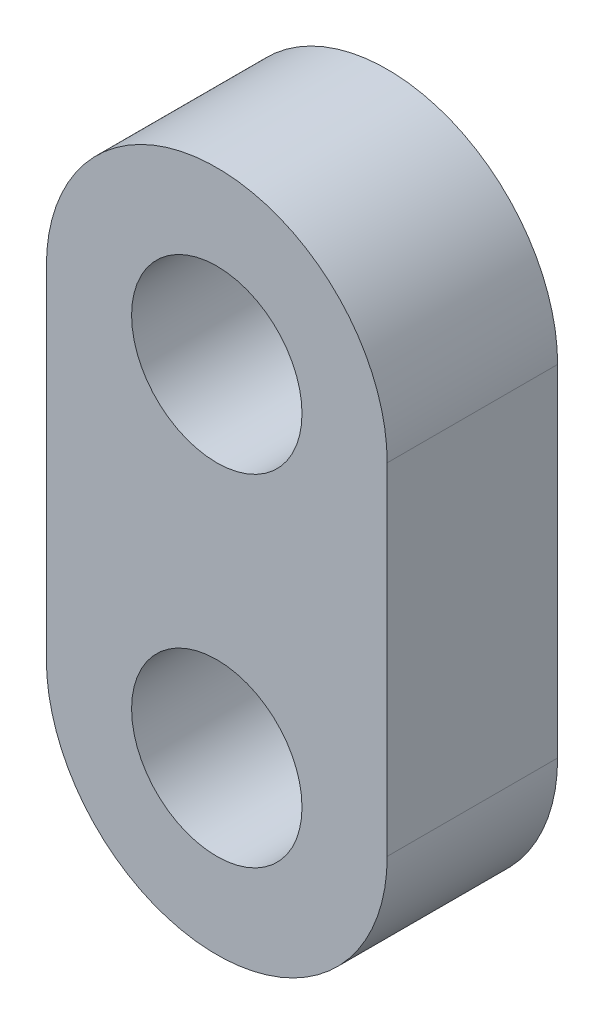
SolidWorks part; units mm, degrees
ref_plane "Front Plane" through (0, 0, 0) normal (0, 0, 1) x (1, 0, 0)
ref_plane "Top Plane" through (0, 0, 0) normal (0, 1, 0) x (1, 0, 0)
ref_plane "Right Plane" through (0, 0, 0) normal (1, 0, 0) x (0, 0, -1)
sketch "Sketch1" plane through (0, 0, 0) normal (0, 0, 1) x (1, 0, 0)
  line L0 (0, 0) -> (0, 12.7) construction
  line L1 (-6.35, 12.7) -> (-6.35, 0)
  line L2 (6.35, 12.7) -> (6.35, 0)
  circle A0 centre (0, 0) radius 3.175
  circle A1 centre (0, 12.7) radius 3.175
  arc A2 (6.35, 12.7) -> (-6.35, 12.7) centre (0, 12.7) ccw
  arc A3 (-6.35, 0) -> (6.35, 0) centre (0, 0) ccw
  dimension "D2" = 6.35
  dimension "D3" = 6.35
  dimension "D4" = 12.7
  dimension "D5" = 12.7
  dimension "D1" = 12.7
extrude "Boss-Extrude1" add sketch "Sketch1" along normal blind 6.35
